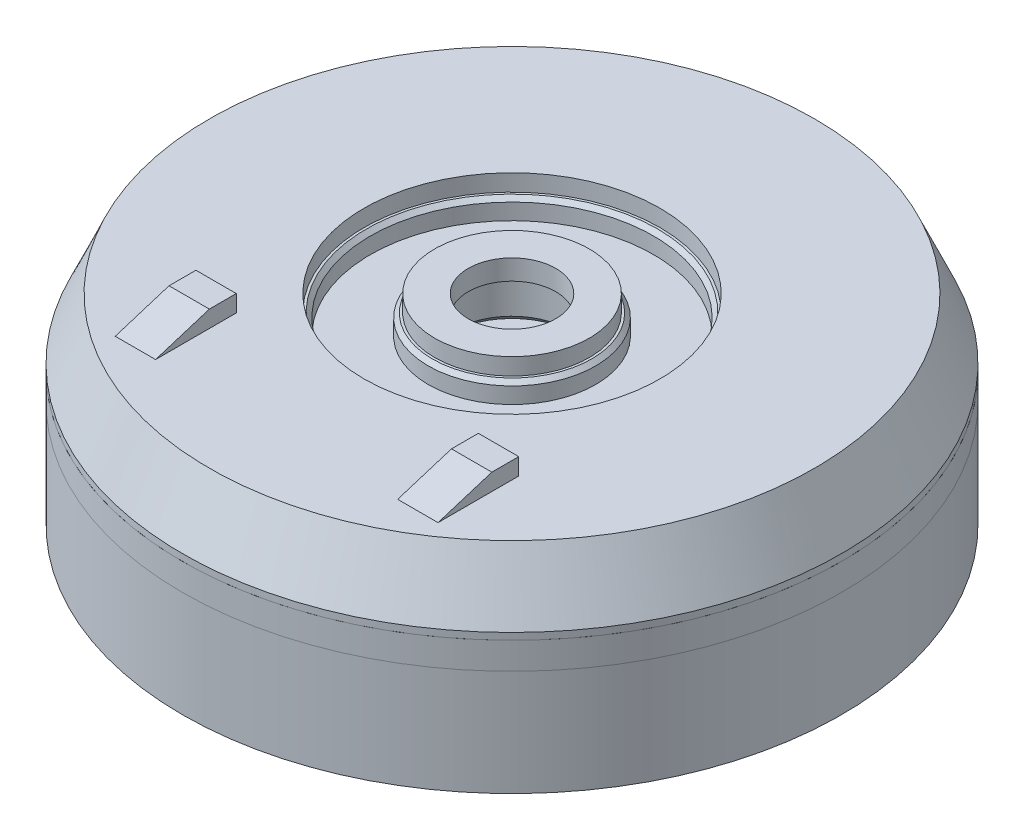
SolidWorks part; units mm, degrees
ref_plane "Front Plane" through (0, 0, 0) normal (0, 0, 1) x (1, 0, 0)
ref_plane "Top Plane" through (0, 0, 0) normal (0, 1, 0) x (1, 0, 0)
ref_plane "Right Plane" through (0, 0, 0) normal (1, 0, 0) x (0, 0, -1)
sketch "Sketch1" plane through (0, 0, 0) normal (0, 1, 0) x (1, 0, 0)
  circle A0 centre (0, 0) radius 49
  circle A1 centre (0, 0) radius 39
  dimension "D1" = 98
  dimension "D2" = 10
extrude "Boss-Extrude1" add sketch "Sketch1" along normal blind 15.75
sketch "Sketch2" plane through (0, 0, 0) normal (0, -1, 0) x (1, 0, 0)
  circle A0 centre (0, 0) radius 39 construction
  circle A1 centre (0, 0) radius 39
extrude "Boss-Extrude2" add sketch "Sketch2" against normal blind 1
sketch "Sketch3" plane through (0, 1, 0) normal (0, 1, 0) x (1, 0, 0)
  circle A0 centre (0, 0) radius 20
  dimension "D1" = 40
extrude "Boss-Extrude3" add sketch "Sketch3" along normal up to surface (14.75 mm away) up to face at (0, 15.75, 49)
sketch "Sketch4" plane through (0, 15.75, 0) normal (0, 1, 0) x (1, 0, 0)
  line L1 (-7.5, -8) -> (7.5, -8)
  line L2 (-7.5, -8) -> (-7.5, 8)
  line L3 (-7.5, 8) -> (7.5, 8)
  line L4 (7.5, -8) -> (7.5, 8)
  line L5 (-7.5, -8) -> (7.5, 8) construction
  line L6 (-7.5, 8) -> (7.5, -8) construction
  point P0 (0, 0)
  dimension "D1" = 15
  dimension "D2" = 16
extrude "Cut-Extrude1" cut sketch "Sketch4" against normal blind 8
sketch "Sketch5" plane through (0, 0, 0) normal (0, -1, 0) x (1, 0, 0)
  line L1 (-9, -9) -> (9, -9)
  line L2 (-9, -9) -> (-9, 9)
  line L3 (-9, 9) -> (9, 9)
  line L4 (9, -9) -> (9, 9)
  line L5 (-9, -9) -> (9, 9) construction
  line L6 (-9, 9) -> (9, -9) construction
  point P0 (0, 0)
  dimension "D1" = 18
  dimension "D2" = 18
extrude "Cut-Extrude2" cut sketch "Sketch5" against normal offset from surface (5.75 mm away) 2 up to face at (0, 7.75, 0)
sketch "Sketch6" plane through (0, 7.75, 0) normal (0, 1, 0) x (1, 0, 0)
  line L0 (0, 0) -> (-7.5, 0) construction
  line L1 (-7.5, 8) -> (-7.5, -8) construction
  line L2 (0, 0) -> (7.5, 0) construction
  line L3 (7.5, -8) -> (7.5, 8) construction
  line L4 (7.5, -8) -> (7.5, 8) construction
  line L5 (-5.5, 6) -> (-3.5, 6)
  line L6 (-5.5, 6) -> (-5.5, -6)
  line L7 (-5.5, -6) -> (-3.5, -6)
  line L8 (-3.5, 6) -> (-3.5, -6)
  line L9 (-5.5, 6) -> (-3.5, -6) construction
  line L10 (-5.5, -6) -> (-3.5, 6) construction
  line L11 (5.5, 6) -> (3.5, 6)
  line L12 (5.5, 6) -> (5.5, -6)
  line L13 (5.5, -6) -> (3.5, -6)
  line L14 (3.5, 6) -> (3.5, -6)
  line L15 (5.5, 6) -> (3.5, -6) construction
  line L16 (5.5, -6) -> (3.5, 6) construction
  point P5 (-4.5, 0)
  point P13 (4.5, 0)
  dimension "D1" = 2
  dimension "D2" = 2
  dimension "D3" = 12
  dimension "D4" = 2
extrude "Cut-Extrude3" cut sketch "Sketch6" against normal through all
sketch "Sketch7" plane through (0, 15.75, 0) normal (0, 1, 0) x (1, 0, 0)
  circle A0 centre (0, 0) radius 48
  circle A1 centre (0, 0) radius 39
  circle A2 centre (0, 0) radius 39 construction
  dimension "D1" = 96
extrude "Cut-Extrude4" cut sketch "Sketch7" against normal blind 1.6
sketch "Sketch8" plane through (0, 15.75, 0) normal (0, 1, 0) x (1, 0, 0)
  circle A0 centre (0, 0) radius 49 construction
  circle A1 centre (0, 0) radius 49
  circle A2 centre (0, 0) radius 48 construction
  circle A3 centre (0, 0) radius 48
extrude "Boss-Extrude4" add sketch "Sketch8" along normal blind 3 separate body
sketch "Sketch9" plane through (0, 18.75, 0) normal (0, 1, 0) x (1, 0, 0)
  circle A0 centre (0, 0) radius 49 construction
  circle A1 centre (0, 0) radius 49
  circle A2 centre (0, 0) radius 39 construction
  circle A3 centre (0, 0) radius 39
extrude "Boss-Extrude5" add sketch "Sketch9" along normal blind 1
sketch "Sketch11" plane through (0, 0, 0) normal (1, 0, 0) x (0, 0, -1)
  line L0 (0, 19.75) -> (0, 29.75)
  line L1 (39, 19.75) -> (-39, 19.75) construction
  line L2 (0, 29.75) -> (45, 29.75)
  line L3 (45, 29.75) -> (49, 20.75)
  line L4 (49, 20.75) -> (49, 19.75)
  line L5 (49, 19.75) -> (0, 19.75)
  line L6 (0, 29.75) -> (0, 41.2811) construction
  line L7 (0, 0) -> (0, 48.9141) construction
  line L8 (49, 19.75) -> (-49, 19.75) construction
  line L9 (49, 19.75) -> (-49, 19.75)
  point P14 (0, 0)
  dimension "D1" = 10
  dimension "D2" = 1
  dimension "D3" = 45
revolve "Revolve1" add sketch "Sketch11" angle 360 about L7
sketch "Sketch12" plane through (0, 29.75, 0) normal (0, 1, 0) x (1, 0, 0)
  circle A0 centre (0, 0) radius 11.5
  circle A1 centre (0, 0) radius 22
  dimension "D1" = 23
  dimension "D2" = 44
extrude "Cut-Extrude5" cut sketch "Sketch12" against normal blind 5.5
sketch "Sketch13" plane through (0, 29.75, 0) normal (0, 1, 0) x (1, 0, 0)
  circle A0 centre (0, 0) radius 8.6
  dimension "D1" = 17.2
extrude "Cut-Extrude6" cut sketch "Sketch13" against normal up to surface (10 mm away) up to face at (0, 19.75, -49)
sketch "Sketch14" plane through (0, 29.75, 0) normal (0, 1, 0) x (1, 0, 0)
  circle A0 centre (0, 0) radius 8.6 construction
  circle A1 centre (0, 0) radius 8.6
  circle A2 centre (0, 0) radius 6.5
  dimension "D1" = 13
extrude "Boss-Extrude6" add sketch "Sketch14" against normal blind 3
sketch "Sketch15" plane through (0, 24.25, 0) normal (0, 1, 0) x (1, 0, 0)
  circle A0 centre (0, 0) radius 12.45
  circle A1 centre (0, 0) radius 21.05
  circle A2 centre (0, 0) radius 22 construction
  circle A3 centre (0, 0) radius 22
  circle A4 centre (0, 0) radius 11.5 construction
  circle A5 centre (0, 0) radius 11.5
  circle M5 centre (0, 0) radius 11.5
  circle M6 centre (0, 0) radius 22
  dimension "D1" = 24.9
  dimension "D2" = 42.1
extrude "Boss-Extrude7" add sketch "Sketch15" along normal blind 3 contours A1 M6 | A0 M5 region at (-12.0979, 24.25, 0) region at (-21.3777, 24.25, 0)
chamfer "Chamfer1" distance 0.6 angle 45 2 edges at (0, 27.25, 21.05) (0, 27.25, 12.45)
chamfer "Chamfer2" distance 1 angle 45 1 edges at (0, 19.75, 8.6)
sketch "Sketch16" plane through (0, 29.75, 0) normal (0, 1, 0) x (1, 0, 0)
  line L0 (0, -23) -> (-27, -23) construction
  line L1 (-27, -23) -> (-27, 23) construction
  line L2 (-27, 23) -> (0, 23) construction
  line L3 (-18.2, 27) -> (2.7, 27) construction
  line L4 (-18.2, 27) -> (2.7, 27) construction
  line L5 (0, 0) -> (0, -60.6841) construction
  line L6 (-24, -23) -> (-18, -23)
  line L7 (-24, -23) -> (-24, -35)
  line L8 (-24, -35) -> (-18, -35)
  line L9 (-18, -23) -> (-18, -35)
  line L10 (0, -200000) -> (0, 200104.7382) construction
  line L11 (24, -23) -> (18, -23)
  line L12 (24, -23) -> (24, -35)
  line L13 (24, -35) -> (18, -35)
  line L14 (18, -23) -> (18, -35)
  arc A0 (-23, 0) -> (23, 0) centre (0, 0) ccw construction
  arc A1 (-23, 0) -> (23, 0) centre (0, 0) ccw construction
  circle A6 centre (0, 0) radius 23 construction
  dimension "D2" = 4
  dimension "D3" = 6
  dimension "D1" = 4
  dimension "D4" = 3
  dimension "D5" = 12
extrude "Boss-Extrude8" add sketch "Sketch16" along normal blind 2.5
sketch "Sketch17" plane through (-24, 0, 0) normal (-1, 0, 0) x (0, 0, 1)
  line L0 (35, 29.75) -> (27, 32.25)
  line L1 (23, 32.25) -> (35, 32.25) construction
  line L2 (27, 32.25) -> (35, 32.25)
  line L3 (35, 32.25) -> (35, 29.75)
  line L4 (23, 32.25) -> (23, 29.75) construction
  dimension "D1" = 4
extrude "Cut-Extrude7" cut sketch "Sketch17" against normal through all
